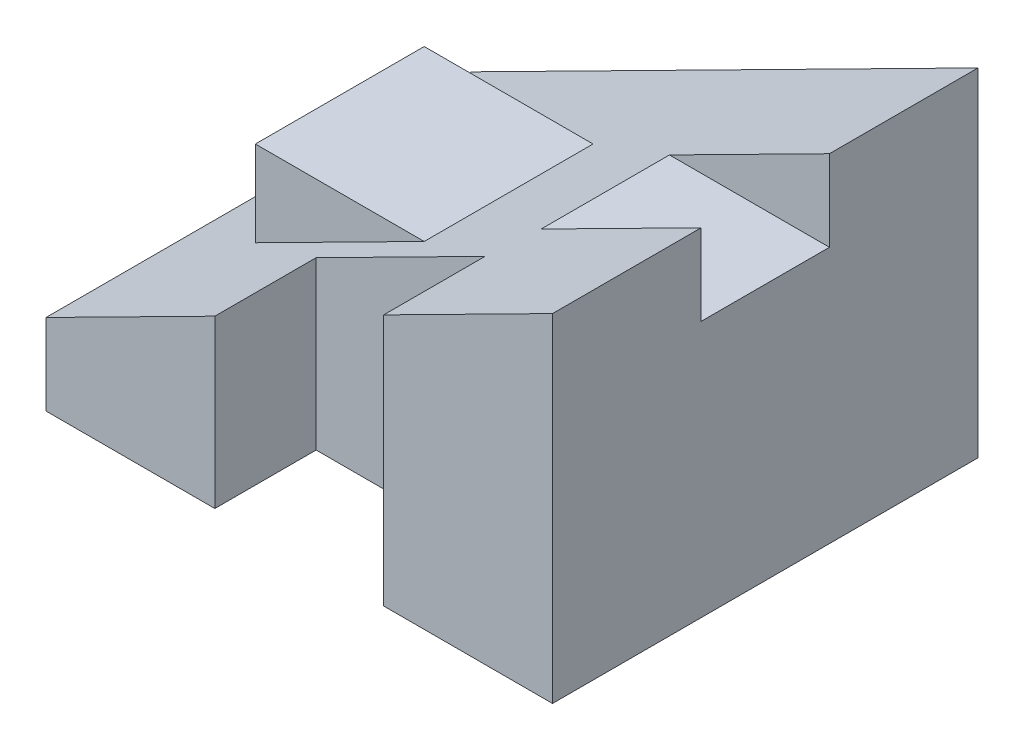
SolidWorks part; units mm, degrees
ref_plane "Front Plane" through (0, 0, 0) normal (0, 0, 1) x (1, 0, 0)
ref_plane "Top Plane" through (0, 0, 0) normal (0, 1, 0) x (1, 0, 0)
ref_plane "Right Plane" through (0, 0, 0) normal (1, 0, 0) x (0, 0, -1)
sketch "Sketch1" plane through (0, 0, 0) normal (0, 1, 0) x (1, 0, 0)
  line L0 (25, 0) -> (25, 15)
  line L1 (0, 0) -> (75, 0)
  line L2 (0, 0) -> (0, 63)
  line L3 (0, 63) -> (75, 63)
  line L4 (75, 0) -> (75, 63)
  line L5 (25, 15) -> (50, 15)
  line L6 (50, 15) -> (50, 0)
  line L8 (12, 19) -> (37, 19)
  line L9 (12, 19) -> (12, 44)
  line L10 (12, 44) -> (37, 44)
  line L11 (37, 19) -> (37, 44)
  dimension "D1" = 75
  dimension "D2" = 63
  dimension "D3" = 25
  dimension "D4" = 25
  dimension "D5" = 15
  dimension "D6" = 25
  dimension "D7" = 19
  dimension "D8" = 12
extrude "Boss-Extrude1" add sketch "Sketch1" along normal blind 50 contours L5 L6 L1 L4 L3 L2 L0 L11 L8 L9 L10 region at (39.6812, 0, -33.9161)
sketch "Sketch2" plane through (0, 0, -63) normal (0, 0, -1) x (-1, 0, 0)
  line L1 (0, 50) -> (0, 0) construction
  line L2 (0, 12) -> (-75, 50)
  line L5 (-75, 50) -> (0, 50)
  line L6 (0, 50) -> (0, 12)
extrude "Cut-Extrude2" cut sketch "Sketch2" against normal up to next
sketch "Sketch3" plane through (75, 0, 0) normal (1, 0, 0) x (0, 0, -1)
  line L0 (22, 50) -> (22, 38)
  line L1 (0, 50) -> (63, 50) construction
  line L2 (22, 38) -> (41, 38)
  line L3 (41, 38) -> (41, 50)
  line L4 (0, 50) -> (0, 0) construction
  line L5 (63, 50) -> (63, 0) construction
  line L6 (22, 50) -> (41, 50)
  dimension "D1" = 22
  dimension "D2" = 22
  dimension "D3" = 12
extrude "Cut-Extrude3" cut sketch "Sketch3" against normal up to next
extrude "Boss-Extrude2" add sketch "Sketch1<3>" along normal blind 31 contours L8 L11 L10 L9 region at (24.5, 0, -31.5)
sketch "Sketch1<3>" plane through (0, 0, 0) normal (0, 1, 0) x (1, 0, 0) same geometry as "Sketch1"
sketch "Sketch4" plane through (0, 0, -19) normal (0, 0, 1) x (1, 0, 0)
  line L0 (37, 30.7467) -> (12, 30.7467)
  line L1 (12, 31) -> (12, 18.08) construction
  line L2 (12, 30.7467) -> (12, 31)
  line L3 (12, 31) -> (37, 31)
  line L4 (37, 31) -> (37, 30.7467)
extrude "Cut-Extrude4" cut sketch "Sketch4" against normal up to next
